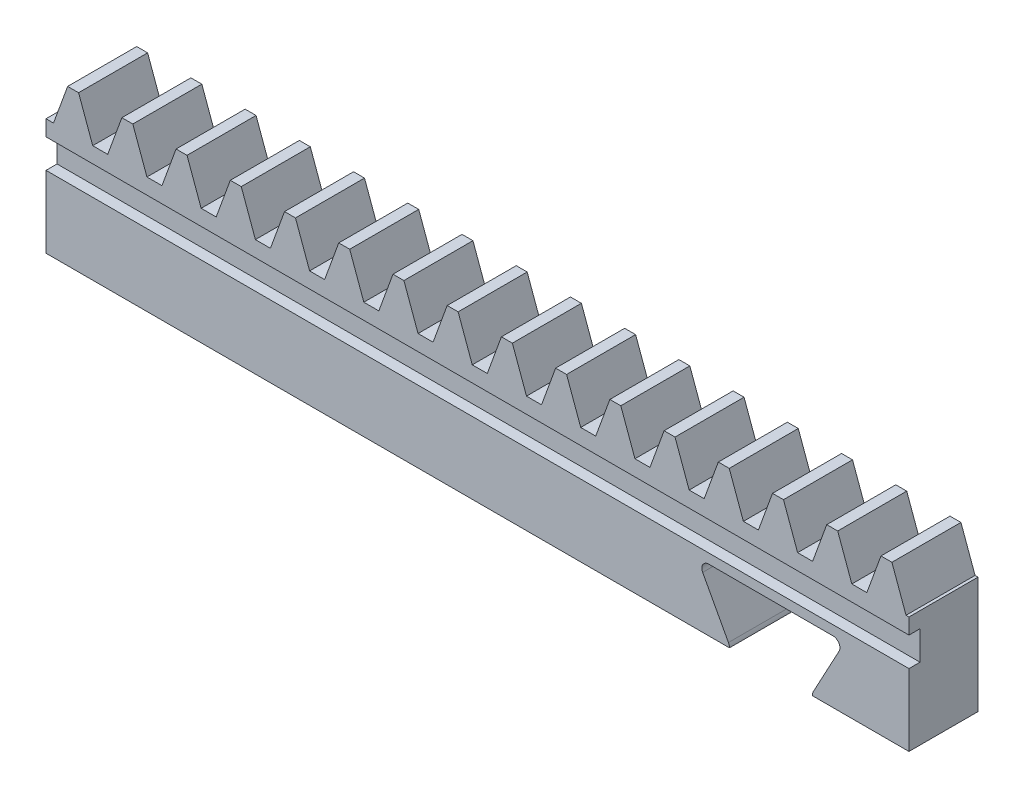
SolidWorks part; units mm, degrees
extrude "Blank" add sketch "BlankSke" against normal blind 10
sketch "BlankSke" plane through (0, 0, 0) normal (0, 0, 1) x (1, 0, 0)
  line L1 (0, 0) -> (125, 0)
  line L2 (0, 0) -> (0, 22.5)
  line L3 (0, 22.5) -> (125, 22.5)
  line L4 (125, 0) -> (125, 22.5)
  dimension "Length" = 125
ref_plane "Plane1" through (0, 0, 0) normal (0, 0, 1) x (1, 0, 0)
ref_plane "Plane2" through (0, 0, 0) normal (0, 1, 0) x (1, 0, 0)
ref_plane "Plane3" through (0, 0, 0) normal (1, 0, 0) x (0, 0, -1)
other "Configuration Table"
sketch "HoldingSke" plane through (0, 0, 0) normal (0, 1, 0) x (1, 0, 0)
  line L0 (0, 0) -> (0.0557, 0.3961)
  line L1 (-15, 0) -> (100, 0) construction
  line L2 (0, 0) -> (-2.1039, 2.3779)
  line L3 (0, 0) -> (-11.863, 4.5341)
  line L4 (0, 0) -> (8.2587, 2.5249)
  line L5 (0, 0) -> (-23.7986, -8.8762)
  line L6 (0, 0) -> (-10.5278, -7.1032)
  line L9 (-71.009, 38.7566) -> (46.4526, 81.5091)
  line L10 (-76.2, 4.8779) -> (-56.2, 4.8779)
  line L11 (0, 0) -> (-10, 0)
  line L12 (-76.2, 101.6) -> (-76.113, 101.6)
  line L13 (24.9733, 27.94) -> (52.9518, 28.4284)
  line L14 (24.9733, 27.94) -> (24.9743, 27.94)
  line L15 (24.9733, 27.94) -> (100.4006, 29.5858)
  circle A0 centre (0, 0) radius 19.05
  circle A1 centre (0, 0) radius 10
  circle A2 centre (0, 0) radius 12.7
  dimension "Num_teeth" = 17
  dimension "Width" = 10
  dimension "Length" = 125
  dimension "Pitch_height" = 20
sketch "TooCutSkeIll" plane through (0, 0, 0) normal (0, 0, 1) x (1, 0, 0)
  line L0 (-3.1105, 22.4342) -> (-1.237, 17.2869)
  line L1 (-0.6488, 16.875) -> (0.6488, 16.875)
  line L2 (1.237, 17.2869) -> (3.1105, 22.4342)
  line L3 (125, 22.5) -> (0, 22.5) construction
  line L4 (0, 0) -> (0, 64.897) construction
  line L5 (-13.208, 20) -> (12.954, 20) construction
  line L6 (0, 0) -> (125, 0) construction
  line L7 (2.2245, 20) -> (2.2245, 48.7463) construction
  line L8 (-2.2245, 20) -> (-2.2245, 48.7463) construction
  line L9 (3.2044, 22.5) -> (3.2044, 22.5254)
  line L10 (-3.2044, 22.5) -> (-3.2044, 22.5254)
  line L11 (-3.2044, 22.5254) -> (3.2044, 22.5254)
  arc A0 (0.6488, 16.875) -> (1.237, 17.2869) centre (0.6488, 17.501) ccw
  arc A1 (-1.237, 17.2869) -> (-0.6488, 16.875) centre (-0.6488, 17.501) ccw
  arc A2 (3.2044, 22.5) -> (3.1105, 22.4342) centre (3.2044, 22.4) ccw
  arc A3 (-3.1105, 22.4342) -> (-3.2044, 22.5) centre (-3.2044, 22.4) ccw
  dimension "Addendum_plus" = 2.5254
  dimension "Pitch_height" = 20
  dimension "Pressure_angle" = 20
  dimension "Gap_width" = 4.449
  dimension "Dedendum" = 3.125
extrude "ToothCutIll" [suppressed] cut sketch "TooCutSkeIll" against normal through all
sketch "TooCutSkeSim" plane through (0, 0, 0) normal (0, 0, 1) x (1, 0, 0)
  line L0 (1.0871, 16.875) -> (-1.0871, 16.875)
  line L1 (3.1437, 22.5254) -> (1.0871, 16.875)
  line L2 (0, 17.4625) -> (0, 53.467) construction
  line L3 (3.1437, 22.5254) -> (-3.1437, 22.5254)
  line L6 (-3.1437, 22.5254) -> (-1.0871, 16.875)
  line L9 (-2.2245, 20) -> (2.2245, 20) construction
  line L10 (0, 0) -> (125, 0) construction
  line L11 (2.2245, 20) -> (2.2245, 53.467) construction
  line L12 (-2.2245, 20) -> (-2.2245, 53.467) construction
  dimension "Addendum_plus" = 2.5254
  dimension "Pitch_height" = 20
  dimension "Pressure_angle" = 20
  dimension "Gap_width" = 4.449
  dimension "Dedendum" = 3.125
extrude "ToothCutSim" cut sketch "TooCutSkeSim" against normal through all
pattern_linear "TeethCuts" count 17 spacing 7.854 along (1, 0, 0) of "ToothCutIll", "ToothCutSim"
sketch "Sketch1" plane through (0, 0, 0) normal (1, 0, 0) x (0, 0, -1)
  line L3 (0, 14.6) -> (0, 10.4)
  line L6 (0, 10.4) -> (1.6, 10.4)
  line L7 (1.6, 10.4) -> (1.6, 14.6)
  line L8 (1.6, 14.6) -> (0, 14.6)
  line L9 (0, 10.4) -> (1.6, 10.4)
  line L10 (1.6, 10.4) -> (1.6, 14.6)
  line L11 (1.6, 14.6) -> (0, 14.6)
  dimension "D1" = 0.1
extrude "Standoffs" cut sketch "Sketch1" along normal up to surface (125 mm away) up to face at (125, 8.4375, -5)
sketch "Sketch2" plane through (0, 0, -10) normal (0, 0, -1) x (-1, 0, 0)
  line L0 (-105, 0) -> (-105, 15.6235) construction
  line L1 (0, 0) -> (-125, 0) construction
  line L2 (-125, 0) -> (-125, 16.875) construction
  line L3 (-96, 9) -> (-114, 9)
  line L4 (-114.8806, 7.5261) -> (-111.1493, 0.5923)
  line L5 (-95.1194, 7.5261) -> (-98.8507, 0.5923)
  line L6 (-111, 0) -> (-99, 0)
  line L7 (-128.8, 10.5) -> (75.8, 10.5) construction
  arc A0 (-114, 9) -> (-114.8806, 7.5261) centre (-114, 8) ccw
  arc A1 (-96, 9) -> (-95.1194, 7.5261) centre (-96, 8) cw
  arc A2 (-111, 0) -> (-111.1493, 0.5923) centre (-112.25, 0) ccw
  arc A3 (-99, 0) -> (-98.8507, 0.5923) centre (-97.75, 0) cw
  arc A4 (-111.1493, 0.5923) -> (-111, 0) centre (-112.25, 0) ccw construction
  arc A5 (-98.8507, 0.5923) -> (-99, 0) centre (-97.75, 0) cw construction
  arc A6 (-114.8806, 7.5261) -> (-114, 9) centre (-114, 8) ccw construction
  arc A7 (-95.1194, 7.5261) -> (-96, 9) centre (-96, 8) cw construction
  point P9 (-105, 9)
  dimension "D2" = 2
  dimension "D4" = 2.5
  dimension "D1" = 20
  dimension "D3" = 18
  dimension "D5" = 1.5
  dimension "D6" = 12
  dimension "D7" = 9
extrude "Dovetail" cut sketch "Sketch2" against normal through all both and the other way through all
equation "' \"Module@HoldingSke\" = 6.35"
equation "' \"Num_teeth@HoldingSke\" = 12"
equation "' \"Ap@HoldingSke\" =  20"
equation "' \"Ap@HoldingSke\" = 20"
equation "' \"Width@HoldingSke\" = 0.25 * 25.4"
equation "' \"Show_teeth@HoldingSke\" = 500"
equation "' \"Backlash@HoldingSke\" = 0.009 * 25.4"
equation "' \"Addendum_fac@HoldingSke\" = 1.0"
equation "' \"Dedendum_fac@HoldingSke\" = 1.25"
equation "' \"Dedendum_add@HoldingSke\" = 0.00005 * 25.4"
equation "' \"Clearance_fac@HoldingSke\" = 0.25"
equation "' \"Pitch_height@HoldingSke\" = 1 * 25.4"
equation "' \"Length@HoldingSke\" = 4.71 * 25.4"
equation "\"Pitch@HoldingSke\" = 1 / \"Module@HoldingSke\""
equation "\"MPH@HoldingSke\" = \"Dedendum_fac@HoldingSke\" / \"Pitch@HoldingSke\" + 2 * \"Dedendum_add@HoldingSke\" + 0.002 * 25.4"
equation "\"MPH@HoldingSke\" = ((sgn( \"MPH@HoldingSke\" - \"Pitch_height@HoldingSke\")+1)*( \"MPH@HoldingSke\" - \"Pitch_height@HoldingSke\"))/2 + \"Pitch_height@HoldingSke\""
equation "\"Blank_height@BlankSke\" = \"Pitch_height@HoldingSke\" + \"Addendum_fac@HoldingSke\"  / \"Pitch@HoldingSke\" "
equation "\"Length@BlankSke\" =  \"Length@HoldingSke\""
equation "\"Face_width@Blank\" = \"Width@HoldingSke\""
equation "\"Pressure_angle@TooCutSkeIll\" = \"Ap@HoldingSke\""
equation "\"Addendum_plus@TooCutSkeIll\" =  \"Addendum_fac@HoldingSke\"  / \"Pitch@HoldingSke\" + 0.001 *25.4"
equation "\"Dedendum@TooCutSkeIll\" = \"Dedendum_fac@HoldingSke\"  / \"Pitch@HoldingSke\""
equation "\"Pitch_height@TooCutSkeIll\" =  \"MPH@HoldingSke\""
equation "\"Gap_width@TooCutSkeIll\" = 3.14159265 / 2 / \"Pitch@HoldingSke\" + 6 * \"Backlash@HoldingSke\""
equation "\"Pressure_angle@TooCutSkeSim\" = \"Ap@HoldingSke\""
equation "\"Addendum_plus@TooCutSkeSim\" =  \"Addendum_fac@HoldingSke\"  / \"Pitch@HoldingSke\" + 0.001 * 25.4"
equation "\"Dedendum@TooCutSkeSim\" = \"Dedendum_fac@HoldingSke\"  / \"Pitch@HoldingSke\""
equation "\"Pitch_height@TooCutSkeSim\" =  \"MPH@HoldingSke\""
equation "\"Gap_width@TooCutSkeSim\" = 3.14159265 / 2 / \"Pitch@HoldingSke\" + 6 * \"Backlash@HoldingSke\""
equation "\"Root_fillet@TooCutSkeIll\" = \"Clearance_fac@HoldingSke\" / \"Pitch@HoldingSke\" + \"Dedendum_add@HoldingSke\""
equation "\"Break_rad@TooCutSkeIll\" = 0.02 / \"Pitch@HoldingSke\" * 2"
equation "\"Linear_pitch@TeethCuts\" = 3.14159265 / \"Pitch@HoldingSke\""
equation "\"Num_teeth@HoldingSke\" = int( ( \"Length@HoldingSke\" + 0 ) / (3.14159265 / \"Pitch@HoldingSke\")) + 0.9999  + 1"
equation " \"Num_teeth@TeethCuts\" = int( \"Show_teeth@HoldingSke\" ) + 1"
equation " \"Num_teeth@TeethCuts\" = ((sgn( \"Num_teeth@TeethCuts\" - \"Num_teeth@HoldingSke\" )-1)*( \"Num_teeth@TeethCuts\" - \"Num_teeth@HoldingSke\" ))/-2+ \"Num_teeth@HoldingSke\""
equation " \"Num_teeth@TeethCuts\" = ((sgn( \"Num_teeth@TeethCuts\" - 2.0)+1)*( \"Num_teeth@TeethCuts\" - 2.0))/2 +2.0"
